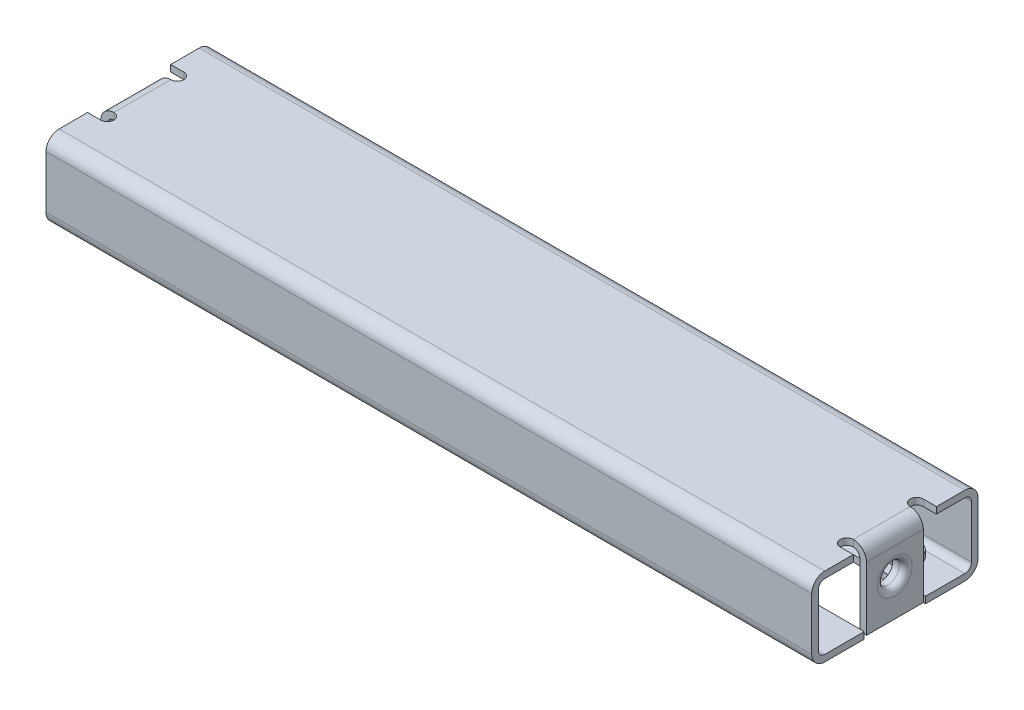
SolidWorks part; units mm, degrees
ref_plane "Front Plane" through (0, 0, 0) normal (0, 0, 1) x (1, 0, 0)
ref_plane "Top Plane" through (0, 0, 0) normal (0, 1, 0) x (1, 0, 0)
ref_plane "Right Plane" through (0, 0, 0) normal (1, 0, 0) x (0, 0, -1)
sketch "Sketch1" plane through (0, 0, 0) normal (1, 0, 0) x (0, 0, -1)
  line L0 (-19, -9) -> (-7, -9)
  line L1 (-19, 9) -> (-19, -9)
  line L2 (-19, 9) -> (19, 9)
  line L3 (19, 9) -> (19, -9)
  line L4 (19, -9) -> (7, -9)
  line L5 (17.5, -7.5) -> (7, -7.5)
  line L6 (17.5, 7.5) -> (17.5, -7.5)
  line L7 (-17.5, 7.5) -> (17.5, 7.5)
  line L8 (-17.5, 7.5) -> (-17.5, -7.5)
  line L9 (-17.5, -7.5) -> (-7, -7.5)
  line L10 (-7, -7.5) -> (-7, -9)
  line L11 (7, -7.5) -> (7, -9)
  line L12 (-17.2256, -9) -> (-7, -9) construction
  line L13 (-19, 5.0268) -> (-19, -11.0657) construction
  line L14 (-17.5, 5.1909) -> (-17.5, -7.5) construction
  line L15 (-14.7009, 7.5) -> (20.0718, 7.5) construction
  line L16 (-14.4108, 9) -> (20.473, 9) construction
  line L17 (17.5, 5.0719) -> (17.5, -7.5) construction
  line L18 (19, 2.7265) -> (19, -7.5894) construction
  line L19 (17.5, -7.5) -> (7, -7.5) construction
  line L20 (20.2876, -9) -> (7, -9) construction
  circle A8 centre (-17.5, -7.5) radius 0 construction
  arc A9 (-19, -11.0657) -> (-17.2256, -9) centre (-20.1502, -8.2826) ccw construction
  arc A10 (-17.5, 5.1909) -> (-14.7009, 7.5) centre (-15.5617, 5.6924) cw construction
  arc A11 (-19, 5.0268) -> (-14.4108, 9) centre (-15.5617, 5.6924) cw construction
  arc A12 (20.0718, 7.5) -> (17.5, 5.0719) centre (19.0279, 6.0296) cw construction
  arc A13 (20.473, 9) -> (19, 2.7265) centre (19.0279, 6.0296) cw construction
  arc A14 (17.5, -7.5) -> (17.5, -7.5) centre (17.5, -7.5) cw construction
  arc A15 (19, -7.5894) -> (20.2876, -9) centre (17.559, -10.1978) cw construction
  point P28 (0, 9)
  point P29 (-19, 0)
  dimension "FIX_2" = 18
  dimension "FIX_3" = 38
  dimension "FIX_5" = 14
  dimension "FIX_4" = 1.5
extrude "Boss-Extrude1" add sketch "Sketch1" along normal mid plane 175
sketch "Sketch2" plane through (0, 9, 0) normal (0, 1, 0) x (1, 0, 0)
  line L0 (84.5, 9.5) -> (87.5, 9.5)
  line L1 (87.5, 9.5) -> (87.5, -9.5)
  line L2 (87.5, -9.5) -> (84.5, -9.5)
  line L3 (84.5, 6.5) -> (84.5, -6.5)
  line L4 (-84.5, 9.5) -> (-87.5, 9.5)
  line L5 (-87.5, 9.5) -> (-87.5, -9.5)
  line L6 (-87.5, -9.5) -> (-84.5, -9.5)
  line L7 (-84.5, 6.5) -> (-84.5, -6.5)
  line L9 (-87.5, 0) -> (87.5, 0) construction
  arc A0 (84.5, 9.5) -> (84.5, 6.5) centre (84.5, 8) ccw
  arc A1 (84.5, -9.5) -> (84.5, -6.5) centre (84.5, -8) cw
  arc A2 (-84.5, 9.5) -> (-84.5, 6.5) centre (-84.5, 8) cw
  arc A3 (-84.5, -9.5) -> (-84.5, -6.5) centre (-84.5, -8) ccw
  dimension "FIX_7" = 1.5
  dimension "FIX_6" = 19
  dimension "FIX_8" = 3
  dimension "W" = 175
extrude "Cut-Extrude1" cut sketch "Sketch2" against normal up to next
sketch "Sketch3" plane through (0, 0, 0) normal (0, 0, 1) x (1, 0, 0)
  line L0 (87.5, -8.5) -> (87.5, 6)
  line L1 (-87.5, -8.5) -> (-87.5, 6)
  line L2 (86, -8.5) -> (86, 6)
  line L3 (-86, -8.5) -> (-86, 6)
  line L4 (-84.5, 9) -> (-84.5, 7.5)
  line L5 (-87.5, -8.5) -> (-86, -8.5)
  line L6 (84.5, 9) -> (84.5, 7.5)
  line L7 (87.5, -8.5) -> (86, -8.5)
  line L8 (-87.5, 0) -> (87.5, 0) construction
  arc A0 (-87.5, 6) -> (-84.5, 9) centre (-84.5, 6) cw
  arc A1 (87.5, 6) -> (84.5, 9) centre (84.5, 6) ccw
  arc A2 (86, 6) -> (84.5, 7.5) centre (84.5, 6) ccw
  arc A3 (-86, 6) -> (-84.5, 7.5) centre (-84.5, 6) cw
  dimension "FIX_12" = 3
  dimension "FIX_10" = 17.5
  dimension "FIX_11" = 9
  dimension "FIX_9" = 1.5
  dimension "W" = 175
extrude "Boss-Extrude2" add sketch "Sketch3" along normal mid plane 13
sketch "Sketch4" plane through (0, 0, 0) normal (0, 0, 1) x (1, 0, 0)
  line L0 (-87.5, 0) -> (87.5, 0) construction
  line L2 (-84.5, 3.55) -> (-84.5, 0)
  line L3 (-87.5, 0) -> (-87.5, 3.55)
  line L4 (-87.5, 3.55) -> (-84.5, 3.55)
  line L5 (87.5, 0) -> (87.5, 3.55)
  line L6 (-84.5, 0) -> (-87.5, 0)
  line L7 (84.5, 3.55) -> (84.5, 0)
  line L8 (84.5, 0) -> (87.5, 0)
  line L9 (84.5, 3.55) -> (87.5, 3.55)
  dimension "FIX_15" = 7.1
  dimension "FIX_14" = 3
  dimension "W" = 175
revolve "Revolve1" add sketch "Sketch4" angle 360 about L0
sketch "Sketch5" plane through (0, 0, 0) normal (0, 0, 1) x (1, 0, 0)
  line L0 (-87.5, 0) -> (87.5, 0) construction
  line L2 (-87.5, 0) -> (87.5, 0)
  line L3 (-87.5, 0) -> (-87.5, 2.4585)
  line L4 (-87.5, 2.4585) -> (87.5, 2.4585)
  line L5 (87.5, 0) -> (87.5, 2.4585)
  dimension "FIX_17" = 4.917
  dimension "W" = 175
revolve "Cut-Revolve1" cut sketch "Sketch5" angle 360 about L0
cosmetic thread "Thread1" parameters "NFIX_1"=6
cosmetic thread "Thread2" parameters "NFIX_2"=6
fillet "Fillet1" radius 1.5 2 edges at (-87.5, 0, 2.4585) (87.5, 0, 2.4585)
sketch "Sketch6" plane through (0, -7.5, 0) normal (0, 1, 0) x (1, 0, 0)
  line L0 (20, -12.5) -> (-20, -12.5) construction
  line L1 (-20, -12.5) -> (-20, 12.5) construction
  line L2 (-20, 12.5) -> (20, 12.5) construction
  line L3 (20, 12.5) -> (20, -12.5) construction
  line L4 (0, 12.5) -> (0, -12.5) construction
  circle A0 centre (20, -12.5) radius 3.15
  circle A1 centre (-20, -12.5) radius 3.15
  circle A2 centre (20, 12.5) radius 3.15
  circle A3 centre (-20, 12.5) radius 3.15
  dimension "FIX_20" = 6.3
  dimension "FIX_21" = 40
  dimension "FIX_22" = 25
extrude "Boss-Extrude3" [suppressed] add sketch "Sketch6" along normal blind 1.5
sketch "Sketch7" [suppressed] plane through (0, -6, 0) normal (0, 1, 0) x (1, 0, 0)
  circle A0 centre (-20, 12.5) radius 2.067
  circle A1 centre (-20, -12.5) radius 2.067
  circle A2 centre (20, -12.5) radius 2.067
  circle A3 centre (20, 12.5) radius 2.067
  dimension "FIX_24" = 4.134
extrude "Cut-Extrude2" [suppressed] cut sketch "Sketch7" against normal through all
cosmetic thread "Thread3" parameters "NFIX_3"=5
cosmetic thread "Thread4" parameters "NFIX_4"=5
cosmetic thread "Thread5" parameters "NFIX_5"=5
cosmetic thread "Thread6" parameters "NFIX_6"=5
fillet "Fillet2" [suppressed] radius 1.5
sketch "Sketch8" plane through (0, -7.5, 0) normal (0, 1, 0) x (1, 0, 0)
  line L0 (-87.5, 0) -> (87.5, 0) construction
  line L1 (37.5, 12.5) -> (77.5, 12.5) construction
  line L2 (-77.5, 12.5) -> (-37.5, 12.5) construction
  line L3 (-77.5, 12.5) -> (-77.5, -12.5) construction
  line L4 (-77.5, -12.5) -> (-37.5, -12.5) construction
  line L5 (-37.5, 12.5) -> (-37.5, -12.5) construction
  line L6 (77.5, 12.5) -> (77.5, -12.5) construction
  line L7 (77.5, -12.5) -> (37.5, -12.5) construction
  line L8 (37.5, -12.5) -> (37.5, 12.5) construction
  line L9 (-57.5, 12.5) -> (-57.5, -12.5) construction
  line L10 (57.5, 12.5) -> (57.5, -12.5) construction
  circle A0 centre (-77.5, 12.5) radius 3.15
  circle A1 centre (-37.5, 12.5) radius 3.15
  circle A2 centre (-77.5, -12.5) radius 3.15
  circle A3 centre (-37.5, -12.5) radius 3.15
  circle A4 centre (37.5, 12.5) radius 3.15
  circle A5 centre (37.5, -12.5) radius 3.15
  circle A6 centre (77.5, -12.5) radius 3.15
  circle A7 centre (77.5, 12.5) radius 3.15
  dimension "FIX_26" = 6.3
  dimension "FIX_27" = 40
  dimension "FIX_28" = 25
  dimension "FIX_32" = 30
  dimension "FIX_33" = 30
  dimension "W-60" = 115
  dimension "W" = 175
extrude "Boss-Extrude4" add sketch "Sketch8" along normal blind 1.5
sketch "Sketch9" plane through (0, -6, 0) normal (0, 1, 0) x (1, 0, 0)
  circle A0 centre (-77.5, 12.5) radius 2.067
  circle A1 centre (-77.5, -12.5) radius 2.067
  circle A2 centre (-37.5, 12.5) radius 2.067
  circle A3 centre (-37.5, -12.5) radius 2.067
  circle A4 centre (37.5, 12.5) radius 2.067
  circle A5 centre (37.5, -12.5) radius 2.067
  circle A6 centre (77.5, -12.5) radius 2.067
  circle A7 centre (77.5, 12.5) radius 2.067
  dimension "FIX_30" = 4.134
extrude "Cut-Extrude3" cut sketch "Sketch9" against normal through all
cosmetic thread "Thread7" parameters "NFIX_7"=5
cosmetic thread "Thread8" parameters "NFIX_8"=5
cosmetic thread "Thread9" parameters "NFIX_9"=5
cosmetic thread "Thread10" parameters "NFIX_10"=5
cosmetic thread "Thread11" parameters "NFIX_11"=5
cosmetic thread "Thread12" parameters "NFIX_12"=5
cosmetic thread "Thread13" parameters "NFIX_13"=5
cosmetic thread "Thread14" parameters "NFIX_14"=5
fillet "Fillet3" radius 1.5 8 edges at (77.5, -9, 14.567) (77.5, -9, -10.433) (37.5, -9, -10.433) (37.5, -9, 14.567) (-37.5, -9, 14.567) (-37.5, -9, -10.433) (-77.5, -9, -10.433) (-77.5, -9, 14.567)
fillet "Fillet4" radius 3 4 edges at (0, -9, -19) (0, 9, -19) (0, -9, 19) (0, 9, 19)
fillet "Fillet5" radius 1.5 4 edges at (0, -7.5, -17.5) (0, 7.5, -17.5) (0, 7.5, 17.5) (0, -7.5, 17.5)
